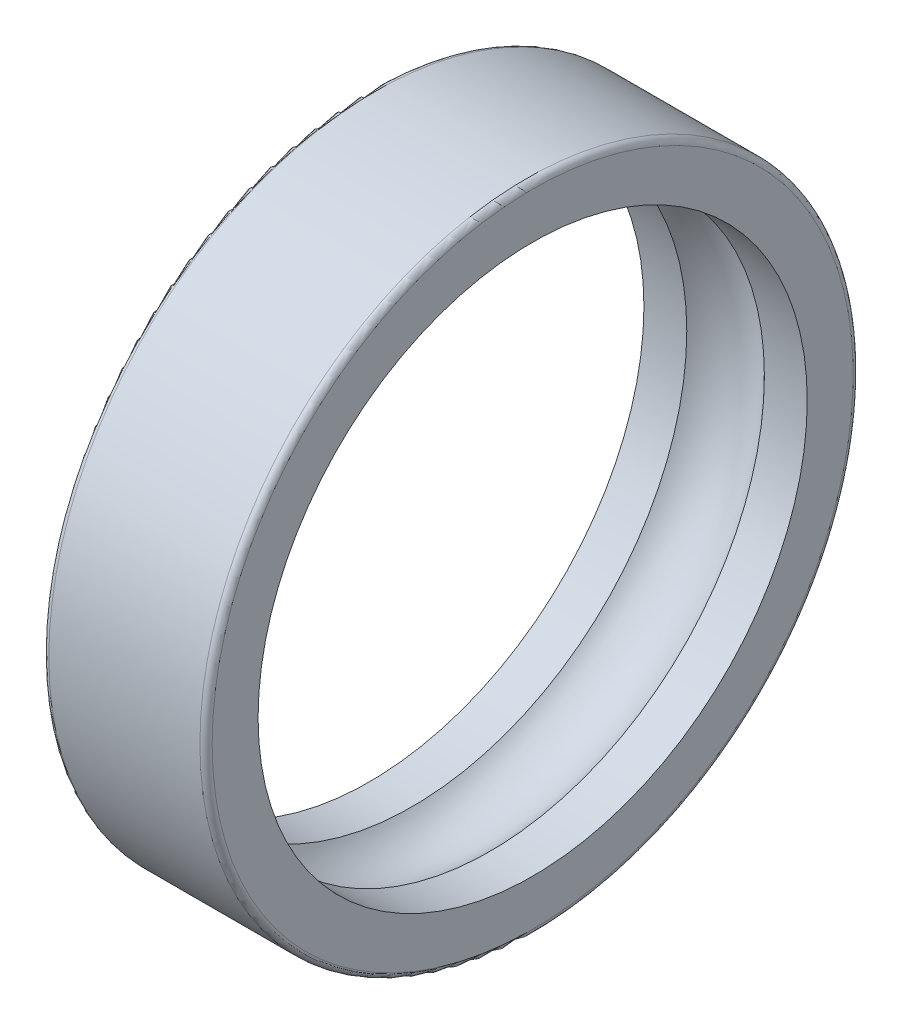
SolidWorks part; units mm, degrees
ref_plane "Plan1" through (0, 0, 0) normal (0, 0, 1) x (1, 0, 0)
ref_plane "Plan2" through (0, 0, 0) normal (0, 1, 0) x (1, 0, 0)
ref_plane "Plan3" through (0, 0, 0) normal (1, 0, 0) x (0, 0, -1)
ref_axis "Axe1" through (-50, 0, 0) along (1, 0, 0)
sketch "Esquisse1" plane through (0, 0, 0) normal (0, 1, 0) x (1, 0, 0)
  line L0 (0, 15.7) -> (0, 7.8) construction
  line L1 (8, 13.45) -> (0, 13.45) construction
  line L2 (8, 15.7) -> (8, 7.8) construction
  line L3 (0.3, 16) -> (7.7, 16) construction
  line L4 (0, 15.7) -> (0, 13.45)
  line L5 (8, 13.45) -> (5.9007, 13.45)
  line L6 (0, 0) -> (12, 0) construction
  line L7 (-50, 0) -> (200, 0) construction
  line L8 (8, 15.7) -> (8, 13.45)
  line L9 (0.3, 16) -> (7.7, 16)
  line L10 (2.0993, 13.45) -> (0, 13.45)
  arc A0 (0.3, 16) -> (0, 15.7) centre (0.3, 15.7) ccw construction
  circle A1 centre (4, 11.75) radius 2.55 construction
  arc A3 (8, 15.7) -> (7.7, 16) centre (7.7, 15.7) ccw construction
  arc A4 (0.3, 16) -> (0, 15.7) centre (0.3, 15.7) ccw
  arc A5 (5.9007, 13.45) -> (2.0993, 13.45) centre (4, 11.75) ccw
  arc A6 (8, 15.7) -> (7.7, 16) centre (7.7, 15.7) ccw
revolve "Base-Révolution" add sketch "Esquisse1" angle 360 about L6
